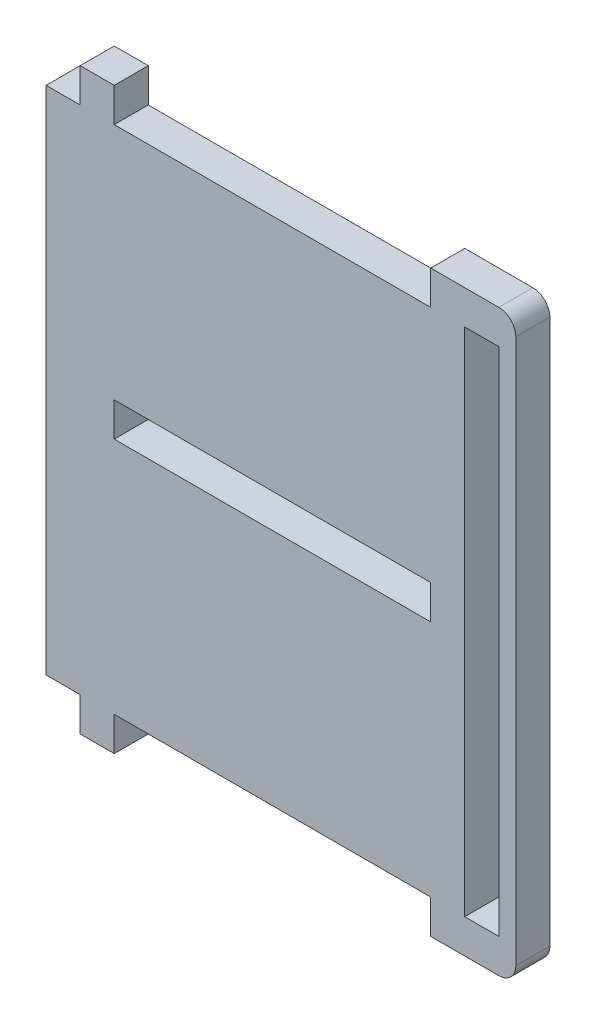
SolidWorks part; units mm, degrees
material "Acrylic (Medium-high impact)"
ref_plane "Front Plane" through (0, 0, 0) normal (0, 0, 1) x (1, 0, 0)
ref_plane "Top Plane" through (0, 0, 0) normal (0, 1, 0) x (1, 0, 0)
ref_plane "Right Plane" through (0, 0, 0) normal (1, 0, 0) x (0, 0, -1)
sketch "Sketch1" plane through (0, 0, 0) normal (0, 0, 1) x (1, 0, 0)
  line L1 (-36.4109, 0) -> (-30.0609, 0)
  line L2 (-36.4109, 0) -> (-36.4109, 6.35)
  line L3 (-36.4109, 107.95) -> (-30.0609, 107.95)
  line L4 (44.8389, 3.175) -> (44.8389, 104.775)
  line L5 (-36.4109, 6.35) -> (-42.7609, 6.35)
  line L7 (-36.4109, 101.6) -> (-42.7609, 101.6)
  line L8 (-42.7609, 6.35) -> (-42.7609, 101.6)
  line L9 (28.9639, 107.95) -> (41.6639, 107.95)
  line L10 (28.9639, 0) -> (41.6639, 0)
  line L11 (-36.4109, 101.6) -> (-36.4109, 107.95)
  line L12 (-30.0609, 101.6) -> (28.9639, 101.6)
  line L13 (28.9639, 101.6) -> (28.9639, 107.95)
  line L14 (28.9639, 107.95) -> (-30.0609, 107.95)
  line L15 (-30.0609, 107.95) -> (-30.0609, 101.6)
  line L16 (-30.0609, 101.6) -> (28.9639, 101.6)
  line L17 (28.9639, 101.6) -> (28.9639, 107.95)
  line L19 (-30.0609, 107.95) -> (-30.0609, 101.6)
  line L20 (-30.0609, 50.8) -> (28.9639, 50.8)
  line L21 (28.9639, 50.8) -> (28.9639, 57.15)
  line L22 (28.9639, 57.15) -> (-30.0609, 57.15)
  line L23 (-30.0609, 57.15) -> (-30.0609, 50.8)
  line L24 (-30.0609, 50.8) -> (28.9639, 50.8)
  line L25 (28.9639, 50.8) -> (28.9639, 57.15)
  line L26 (28.9639, 57.15) -> (-30.0609, 57.15)
  line L27 (-30.0609, 57.15) -> (-30.0609, 50.8)
  line L28 (-30.0609, 0) -> (28.9639, 0)
  line L29 (28.9639, 0) -> (28.9639, 6.35)
  line L30 (28.9639, 6.35) -> (-30.0609, 6.35)
  line L31 (-30.0609, 6.35) -> (-30.0609, 0)
  line L33 (28.9639, 0) -> (28.9639, 6.35)
  line L34 (28.9639, 6.35) -> (-30.0609, 6.35)
  line L35 (-30.0609, 6.35) -> (-30.0609, 0)
  line L37 (35.3139, 101.6) -> (35.3139, 6.35)
  line L38 (35.3139, 6.35) -> (41.6639, 6.35)
  line L39 (41.6639, 6.35) -> (41.6639, 101.6)
  line L40 (41.6639, 101.6) -> (35.3139, 101.6)
  line L41 (35.3139, 101.6) -> (35.3139, 6.35)
  line L42 (35.3139, 6.35) -> (41.6639, 6.35)
  line L43 (41.6639, 6.35) -> (41.6639, 101.6)
  line L44 (41.6639, 101.6) -> (35.3139, 101.6)
  arc A0 (41.6639, 107.95) -> (44.8389, 104.775) centre (41.6639, 104.775) cw
  arc A1 (41.6639, 0) -> (44.8389, 3.175) centre (41.6639, 3.175) ccw
  dimension "D6" = 3.175
  dimension "D1" = 6.35
  dimension "D5" = 3.175
  dimension "D2" = 0
  dimension "D3" = 0
  dimension "D4" = 0
  dimension "D7" = 0
extrude "Boss-Extrude1" add sketch "Sketch1" along normal blind 6.35
